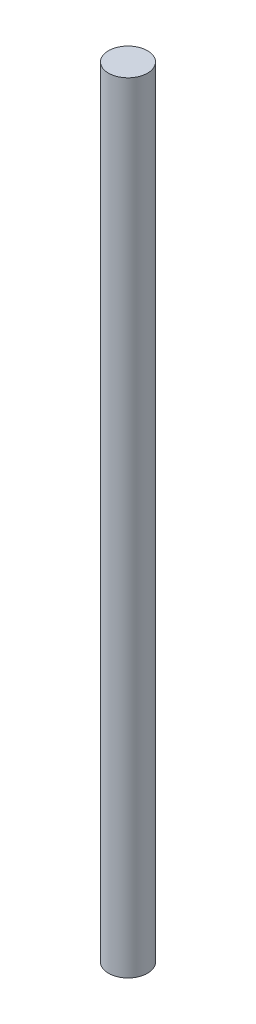
SolidWorks part; units mm, degrees
material "Chrome Stainless Steel"
ref_plane "Front" through (0, 0, 0) normal (0, 0, 1) x (1, 0, 0)
ref_plane "Top" through (0, 0, 0) normal (0, 1, 0) x (1, 0, 0)
ref_plane "Right" through (0, 0, 0) normal (1, 0, 0) x (0, 0, -1)
sketch "Sketch1" plane through (0, 0, 0) normal (0, 1, 0) x (1, 0, 0)
  circle A0 centre (0, 0) radius 2.5
  dimension "D1" = 5
extrude "Boss-Extrude1" add sketch "Sketch1" along normal blind 100 contours A0
